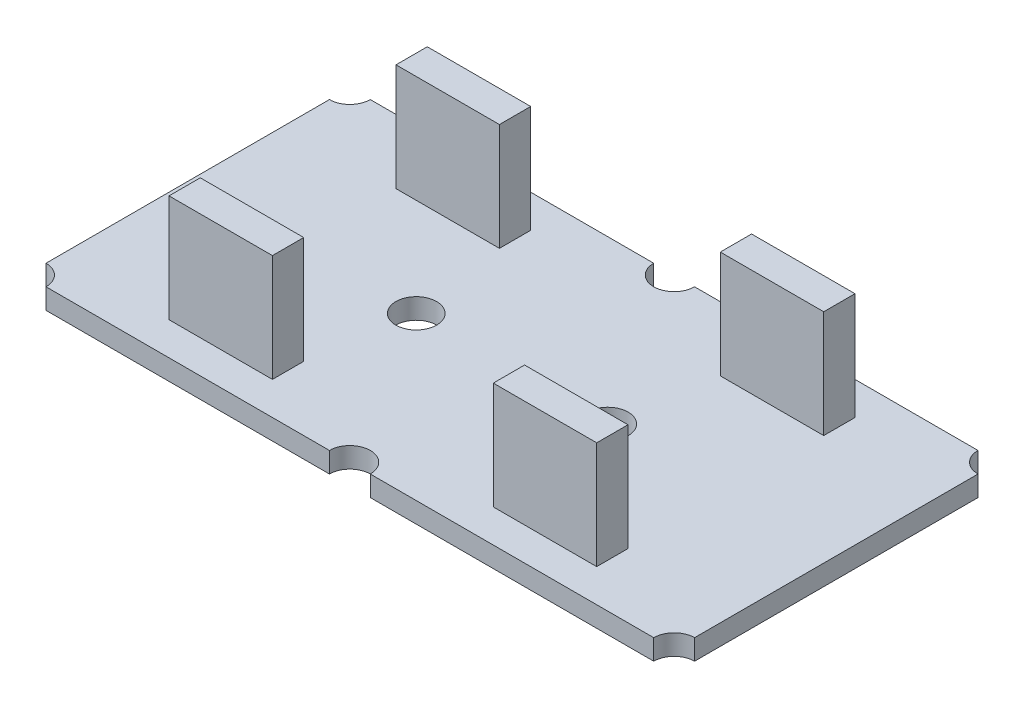
SolidWorks part; units mm, degrees
material "ABS"
ref_plane "Front" through (0, 0, 0) normal (0, 0, 1) x (1, 0, 0)
ref_plane "Top" through (0, 0, 0) normal (0, 1, 0) x (1, 0, 0)
ref_plane "Right" through (0, 0, 0) normal (1, 0, 0) x (0, 0, -1)
sketch "Эскиз1" plane through (0, 0, 0) normal (0, 1, 0) x (1, 0, 0)
  line L0 (25.4, -12.7) -> (25.4, 12.7)
  line L1 (25.4, -12.7) -> (-25.4, -12.7)
  line L2 (25.4, 12.7) -> (-25.4, 12.7)
  line L3 (-25.4, -12.7) -> (-25.4, 12.7)
  line L4 (25.4, -12.7) -> (-25.4, 12.7) construction
  line L5 (25.4, 12.7) -> (-25.4, -12.7) construction
  circle A0 centre (-25.4, 12.7) radius 1.6
  circle A1 centre (0, 12.7) radius 1.6
  circle A2 centre (25.4, 12.7) radius 1.6
  circle A3 centre (25.4, -12.7) radius 1.6
  circle A4 centre (-25.4, -12.7) radius 1.6
  circle A5 centre (0, -12.7) radius 1.6
  point P1 (0, 0)
  dimension "D1" = 50.8
  dimension "D2" = 25.4
extrude "Бобышка-Вытянуть1" add sketch "Эскиз1" against normal blind 1.6 contours A5 L1 A3 L0 A2 L2 A1 A0 L3 A4 region at (0, 0, 0)
sketch "Эскиз2" plane through (0, 0, 0) normal (0, 1, 0) x (1, 0, 0)
  line L0 (12.7, -8.89) -> (-12.7, -8.89) construction
  line L1 (12.7, -8.89) -> (12.7, 8.89) construction
  line L2 (-12.7, -8.89) -> (-12.7, 8.89) construction
  line L3 (12.7, 8.89) -> (-12.7, 8.89) construction
  line L4 (12.7, -8.89) -> (-12.7, 8.89) construction
  line L5 (-12.7, -8.89) -> (12.7, 8.89) construction
  line L6 (0, 0) -> (-29.2027, 0) construction
  line L7 (0, 0) -> (0, 17.1637) construction
  line L8 (-8.65, 7.665) -> (-16.75, 7.665)
  line L9 (-8.65, 7.665) -> (-8.65, 10.115)
  line L10 (-16.75, 7.665) -> (-16.75, 10.115)
  line L11 (-8.65, 10.115) -> (-16.75, 10.115)
  line L12 (-8.65, 7.665) -> (-16.75, 10.115) construction
  line L13 (-16.75, 7.665) -> (-8.65, 10.115) construction
  point P1 (0, 0)
  dimension "D1" = 8.89
  dimension "D2" = 12.7
  dimension "D3" = 2.45
  dimension "D4" = 8.1
extrude "Бобышка-Вытянуть2" add sketch "Эскиз2" along normal blind 8.4
mirror "Зеркальное отражение1" about plane through (0, 0, 0) normal (0, 0, 1) of "Бобышка-Вытянуть2"
mirror "Зеркальное отражение2" about plane through (0, 0, 0) normal (1, 0, 0) of "Зеркальное отражение1", "Бобышка-Вытянуть2"
sketch "Эскиз3" plane through (0, 0, 0) normal (0, 1, 0) x (1, 0, 0)
  circle A0 centre (0, 0) radius 7.5 construction
  circle A1 centre (-7.5, 0) radius 1.6
  circle A2 centre (7.5, 0) radius 1.6
  dimension "D1" = 15
extrude "Вырез-Вытянуть1" cut sketch "Эскиз3" against normal through all
